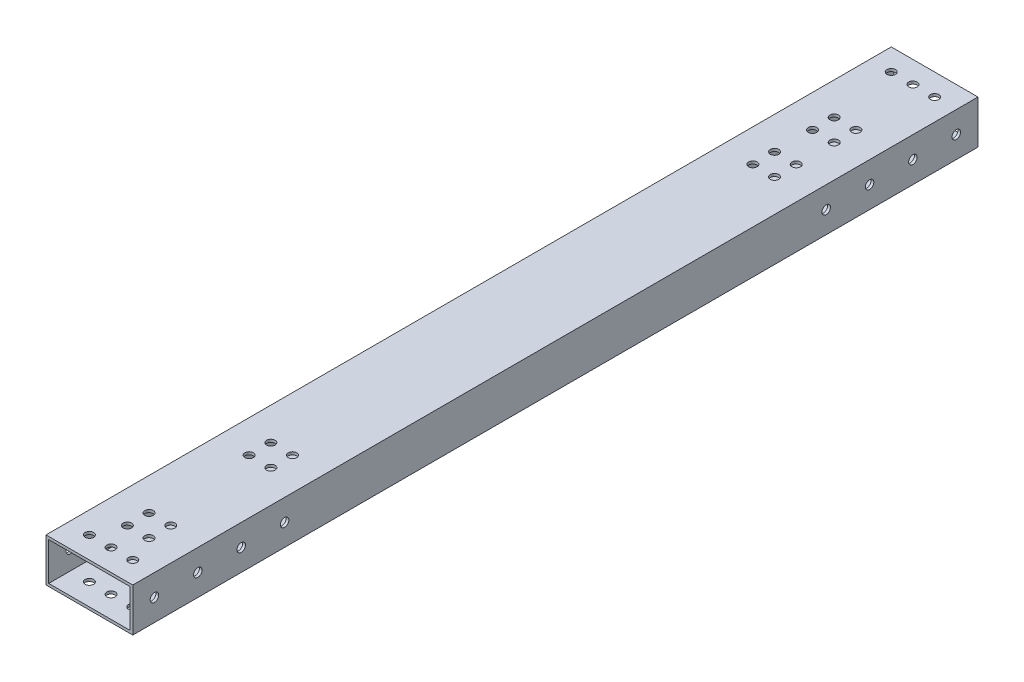
SolidWorks part; units mm, degrees
material "6061-T6 (SS)"
ref_plane "Front Plane" through (0, 0, 0) normal (0, 0, 1) x (1, 0, 0)
ref_plane "Top Plane" through (0, 0, 0) normal (0, 1, 0) x (1, 0, 0)
ref_plane "Right Plane" through (0, 0, 0) normal (1, 0, 0) x (0, 0, -1)
sketch "Sketch1" plane through (0, 0, 0) normal (0, 0, 1) x (1, 0, 0)
  line L0 (-23.8125, 11.1125) -> (23.8125, 11.1125)
  line L1 (-25.4, -12.7) -> (25.4, -12.7)
  line L2 (-25.4, -12.7) -> (-25.4, 12.7)
  line L3 (-25.4, 12.7) -> (25.4, 12.7)
  line L4 (25.4, -12.7) -> (25.4, 12.7)
  line L5 (-25.4, -12.7) -> (25.4, 12.7) construction
  line L6 (-25.4, 12.7) -> (25.4, -12.7) construction
  line L7 (23.8125, -11.1125) -> (23.8125, 11.1125)
  line L8 (-23.8125, -11.1125) -> (23.8125, -11.1125)
  line L9 (-23.8125, -11.1125) -> (-23.8125, 11.1125)
  point P0 (0, 0)
  dimension "D1" = 50.8
  dimension "D2" = 25.4
  dimension "D3" = 1.5875
extrude "Boss-Extrude1" add sketch "Sketch1" along normal mid plane 494.919
sketch "Sketch2" plane through (0, 12.7, 0) normal (0, 1, 0) x (1, 0, 0)
  line L0 (25.4, 247.4595) -> (-25.4, 247.4595) construction
  line L1 (-25.4, 0) -> (25.4, 0) construction
  line L2 (-25.4, -247.4595) -> (-25.4, 247.4595) construction
  line L3 (25.4, -247.4595) -> (25.4, 247.4595) construction
  circle A0 centre (-12.7, 234.7595) radius 2.4892
  circle A1 centre (0, 234.7595) radius 2.4892
  circle A2 centre (12.7, 234.7595) radius 2.4892
  circle A3 centre (12.7, -234.7595) radius 2.4892
  circle A4 centre (0, -234.7595) radius 2.4892
  circle A5 centre (-12.7, -234.7595) radius 2.4892
  point P9 (0, 247.4595)
  dimension "D1" = 4.9784
  dimension "D2" = 12.7
  dimension "D3" = 12.7
  dimension "D4" = 12.7
extrude "Cut-Extrude1" cut sketch "Sketch2" against normal through all
sketch "Sketch3" plane through (25.4, 0, 0) normal (1, 0, 0) x (0, 0, -1)
  line L0 (247.4595, -12.7) -> (247.4595, 12.7) construction
  line L1 (0, 12.7) -> (0, -12.7) construction
  line L2 (-247.4595, 12.7) -> (247.4595, 12.7) construction
  line L3 (-247.4595, -12.7) -> (247.4595, -12.7) construction
  circle A0 centre (234.7595, 0) radius 2.4892
  circle A1 centre (-234.7595, 0) radius 2.4892
  circle A2 centre (209.3595, 0) radius 2.4892
  circle A3 centre (183.9595, 0) radius 2.4892
  circle A4 centre (158.5595, 0) radius 2.4892
  circle A7 centre (-158.5595, 0) radius 2.4892
  circle A8 centre (-183.9595, 0) radius 2.4892
  circle A9 centre (-209.3595, 0) radius 2.4892
  point P5 (247.4595, 0)
  dimension "D1" = 12.7
  dimension "D2" = 4.9784
  dimension "D4" = 25.4
  dimension "D3" = 4
extrude "Cut-Extrude2" cut sketch "Sketch3" against normal through all
sketch "Sketch4" plane through (0, 12.7, 0) normal (0, 1, 0) x (1, 0, 0)
  line L0 (25.4, 247.4595) -> (-25.4, 247.4595) construction
  line L1 (0, 247.4595) -> (0, -247.4595) construction
  line L2 (25.4, -247.4595) -> (-25.4, -247.4595) construction
  line L3 (-6.35, 195.0085) -> (6.35, 195.0085) construction
  circle A0 centre (-6.35, 195.0085) radius 2.4892
  circle A1 centre (6.35, 195.0085) radius 2.4892
  circle A2 centre (-6.35, 182.3085) radius 2.4892
  circle A3 centre (6.35, 182.3085) radius 2.4892
  circle A4 centre (-6.35, 160.0835) radius 2.4892
  circle A5 centre (6.35, 160.0835) radius 2.4892
  circle A6 centre (-6.35, 147.3835) radius 2.4892
  circle A7 centre (6.35, 147.3835) radius 2.4892
  circle A8 centre (-6.35, -218.8616) radius 2.4892
  circle A9 centre (6.35, -218.8616) radius 2.4892
  circle A10 centre (-6.35, -206.1616) radius 2.4892
  circle A11 centre (6.35, -206.1616) radius 2.4892
  circle A12 centre (-6.35, -147.574) radius 2.4892
  circle A13 centre (-6.35, -134.874) radius 2.4892
  circle A14 centre (6.35, -147.574) radius 2.4892
  circle A15 centre (6.35, -134.874) radius 2.4892
  point P32 (0, 195.0085)
  dimension "D1" = 4.9784
  dimension "D2" = 12.7
  dimension "D3" = 58.5876
  dimension "D4" = 12.7
  dimension "D5" = 12.7
  dimension "D6" = 22.225
  dimension "D7" = 12.7
  dimension "D8" = 12.7
  dimension "D9" = 52.451
  dimension "D10" = 28.5979
extrude "Cut-Extrude3" cut sketch "Sketch4" against normal through all
